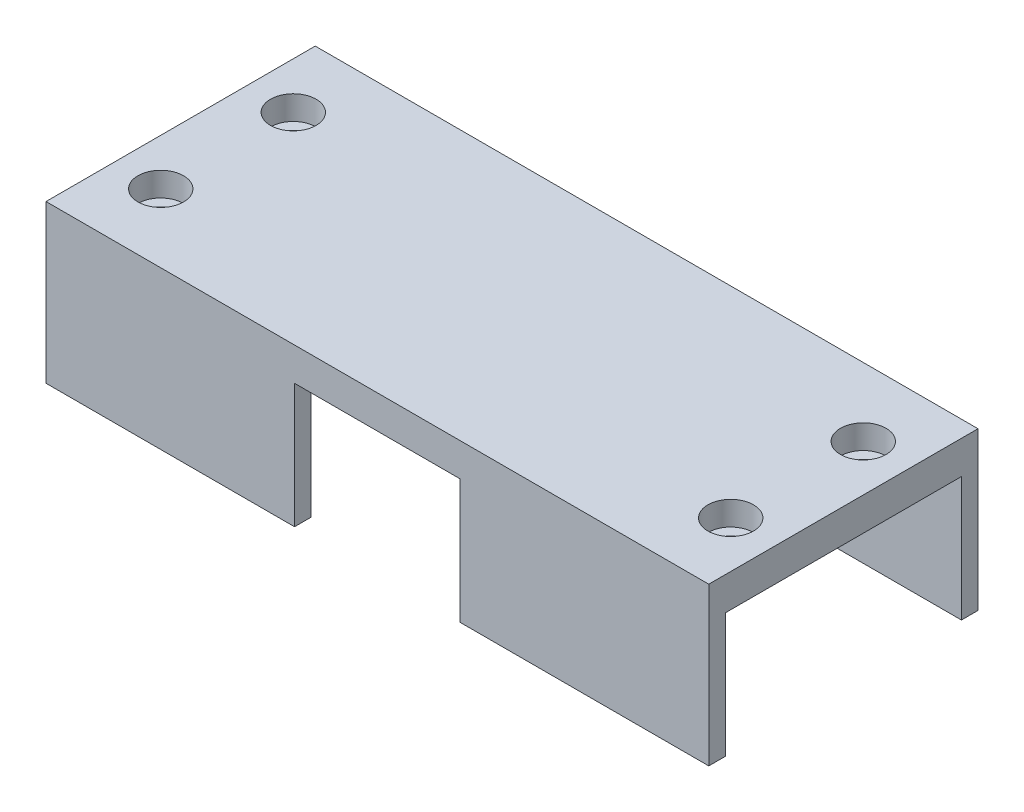
SolidWorks part; units mm, degrees
ref_plane "Front Plane" through (0, 0, 0) normal (0, 0, 1) x (1, 0, 0)
ref_plane "Top Plane" through (0, 0, 0) normal (0, 1, 0) x (1, 0, 0)
ref_plane "Right Plane" through (0, 0, 0) normal (1, 0, 0) x (0, 0, -1)
sketch "Sketch1" plane through (0, 0, 0) normal (0, 1, 0) x (1, 0, 0)
  line L1 (0, 0) -> (80, 0)
  line L2 (0, 0) -> (0, 32.5)
  line L3 (0, 32.5) -> (80, 32.5)
  line L4 (80, 0) -> (80, 32.5)
  dimension "D1" = 32.5
  dimension "D2" = 80
extrude "Boss-Extrude1" add sketch "Sketch1" along normal blind 4
sketch "Sketch4" plane through (0, 4, 0) normal (0, 1, 0) x (1, 0, 0)
  line L0 (40, 32.5) -> (40, -12.4802) construction
  line L1 (80, 32.5) -> (0, 32.5) construction
  line L3 (0, 16.25) -> (122.1673, 16.25) construction
  line L4 (0, 32.5) -> (0, 0) construction
  point P0 (-6.4, 24.25)
  point P12 (5.6, 24.25)
  point P13 (5.6, 8.25)
  point P14 (-6.4, 8.25)
  point P25 (86.4, 8.25)
  point P26 (74.4, 8.25)
  point P27 (74.4, 24.25)
  point P28 (86.4, 24.25)
  dimension "D1" = 2
  dimension "D3" = 12
  dimension "D4" = 16
  dimension "D5" = 8
  dimension "D6" = 34.4
  dimension "D2" = 2
hole_wizard "CBORE for M2.5 Hex Socket Head Cap Screw1" positions "Sketch4" profile "Sketch3" counterbore size "M2.5" standard "DIN" end condition through all
sketch "Sketch3" plane through (-6.4, 4, -24.25) normal (1, 0, 0) x (0, 0, 1)
  line L0 (0, 0) -> (0, 4)
  line L1 (0, 4) -> (1.45, 4)
  line L3 (1.45, 4) -> (1.45, 2.9)
  line L4 (1.45, 2.9) -> (2.75, 2.9)
  line L5 (2.75, 2.9) -> (2.75, 0)
  line L7 (2.75, 0) -> (0, 0)
  line L11 (0, -6.35) -> (0, 107.95) construction
  dimension "Thru Hole Dia." = 2.9
  dimension "Thru Hole Depth" = 4
  dimension "C'Bore Dia." = 5.5
  dimension "C'Bore Depth" = 2.9
sketch "Sketch5" plane through (0, 0, 0) normal (0, -1, 0) x (1, 0, 0)
  line L0 (0, -16.25) -> (80, -16.25) construction
  line L1 (0, 0) -> (80, 0)
  line L2 (0, 0) -> (0, -32.5)
  line L3 (0, -32.5) -> (80, -32.5)
  line L4 (80, 0) -> (80, -32.5)
  line L5 (0, -2) -> (80, -2)
  line L6 (0, -2) -> (0, -30.5)
  line L7 (0, -30.5) -> (80, -30.5)
  line L8 (80, -2) -> (80, -30.5)
  line L9 (0, -16.25) -> (80, -16.25) construction
  line L10 (40, 0) -> (40, -32.5) construction
  line L11 (40, 0) -> (40, -32.5) construction
  line L16 (30, -32.5) -> (50, -32.5)
  line L17 (30, -32.5) -> (30, 0)
  line L18 (30, 0) -> (50, 0)
  line L19 (50, -32.5) -> (50, 0)
  line M25 (0, 0) -> (0, -32.5)
  line M26 (0, -32.5) -> (80, -32.5)
  line M27 (80, -32.5) -> (80, 0)
  line M28 (80, 0) -> (0, 0)
  dimension "D1" = 28.5
  dimension "D2" = 20
extrude "Boss-Extrude2" add sketch "Sketch5" along normal blind 15 contours L5 L17 L1 M25 | L17 L7 M26 M25 | L19 L5 L4 M28 | L19 L7 M26 M27 region at (15, 0, -1) region at (65, 0, -1) region at (15, 0, -31.5) region at (65, 0, -31.5)
